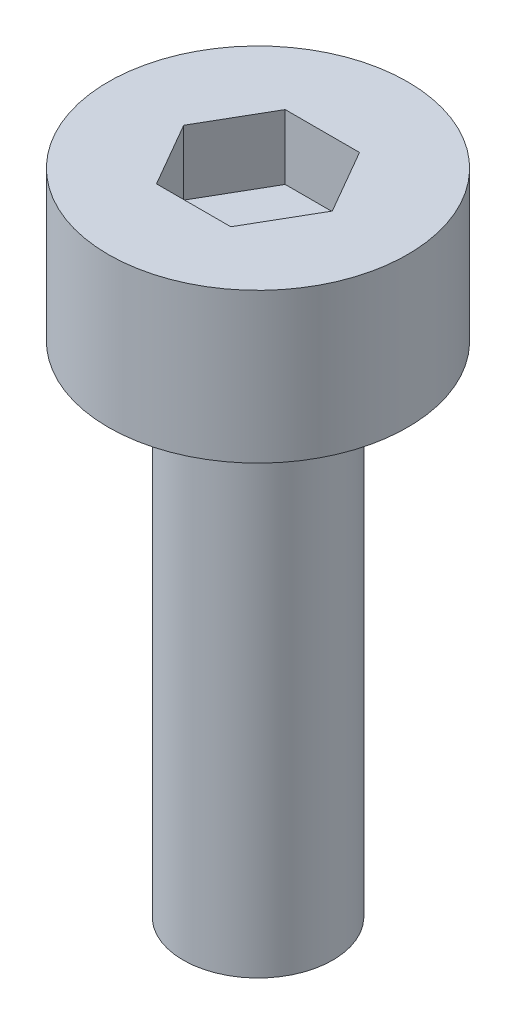
SolidWorks part; units mm, degrees
ref_plane "Front Plane" through (0, 0, 0) normal (0, 0, 1) x (1, 0, 0)
ref_plane "Top Plane" through (0, 0, 0) normal (0, 1, 0) x (1, 0, 0)
ref_plane "Right Plane" through (0, 0, 0) normal (1, 0, 0) x (0, 0, -1)
sketch "Sketch1" plane through (0, 0, 0) normal (0, 1, 0) x (1, 0, 0)
  circle A0 centre (0, 0) radius 1.5
  dimension "D1" = 3
extrude "ScrewShaft" add sketch "Sketch1" along normal blind 10
sketch "Sketch2" plane through (0, 10, 0) normal (0, 1, 0) x (1, 0, 0)
  circle A0 centre (0, 0) radius 3
  dimension "D1" = 6
extrude "Boss-Extrude2" add sketch "Sketch2" along normal blind 3
sketch "Sketch3" plane through (0, 13, 0) normal (0, 1, 0) x (1, 0, 0)
  line L0 (0, 0) -> (0, 1.29) construction
  line L1 (1.4896, 0) -> (0.7448, 1.29)
  line L2 (0.7448, 1.29) -> (-0.7448, 1.29)
  line L3 (-0.7448, 1.29) -> (-1.4896, 0)
  line L4 (-1.4896, 0) -> (-0.7448, -1.29)
  line L5 (-0.7448, -1.29) -> (0.7448, -1.29)
  line L6 (0.7448, -1.29) -> (1.4896, 0)
  circle A0 centre (0, 0) radius 1.29 construction
  dimension "D1" = 2.58
extrude "Cut-Extrude1" cut sketch "Sketch3" against normal blind 1.3
equation "\"X-ROD-SPACING\"=45"
equation "\"Y-ROD-SPACING\"=75"
equation "\"Z-ROD-SPACING\"=17.5"
equation "\"Y-BED-OFFSET\"=2"
equation "\"Y-BED-ROD-INSET\"=3.5"
equation "\"T-SLOT-NUT-FILLET-RADIUS\"=0.25"
equation "\"T-SLOT-SCREW-SHAFT-RADIUS\"=1.75"
equation "\"T-SLOT-SCREW-SHAFT-CUTOUT-LENGTH\"=10.5"
equation "\"T-SLOT-NUT-DEPTH\"=4.2"
equation "\"T-SLOT-NUT-WIDTH\"=3"
equation "\"T-SLOT-NUT-END-DISTANCE\"=8"
equation "\"ACRYLIC-THICKNESS\"=10"
equation "\"ACRYLIC-THICKNESS2\"=4.5"
equation "\"ACRYLIC-TAB-CUTOUT-SIZE\"=\"ACRYLIC-THICKNESS\"+\"ACRYLIC-TAB-TOLERANCE\"*2"
equation "\"ACRYLIC-TAB-WIDTH\"=\"ACRYLIC-THICKNESS\""
equation "\"ACRYLIC-M3-HOLE\"=3.1"
equation "\"SMOOTHROD-CAP-SCREW-DISTANCE\"=20"
equation "\"FRAME-WIDTH-INNER\"=370"
equation "\"NEMA17-HOLE-SPACING\"=31"
equation "\"NEMA17-CENTRAL-CUTOUT\"=22.5"
equation "\"Z-BRACKET-REACH\"=55"
equation "\"TOP-BRACKET-SPACING\"=40"
equation "\"SMOOTHROD-X-LENGTH\"=350"
equation "\"SMOOTHROD-Y-LENGTH\"=350"
equation "\"SMOOTHROD-Z-LENGTH\"=350"
equation "\"SMOOTHROD-TIGHTENING-HEADROOM\"=.25"
equation "\"LEADSCREW-Z-LENGTH\"=300"
equation "\"SCREW-LENGTH-FRAME\"=\"ACRYLIC-THICKNESS\" + 10"
equation "\"SCREW-HEAD-RADIUS\"=6"
equation "\"PRINTED-X-SMOOTHROD-DIAMETER\"=8.2"
equation "\"PRINTED-X-SMOOTHROD-CUTOUT\"=10"
equation "\"PRINTED-X-BASE-HEIGHT\"=10"
equation "\"PRINTED-LM8UU-CUTOUT-SIZE\"=15.25"
equation "\"PRINTED-LM8UU-CUTOUT-LENGTH\"=24.5"
equation "\"PRINTED-X-IDLER-HEIGHT\"=16"
equation "\"PSU-MOUNTING-WIDTH\"=95"
equation "\"PSU-MOUNTING-HEIGHT\"=177"
equation "\"D1@Sketch2\"=\"SCREW-HEAD-RADIUS\""
